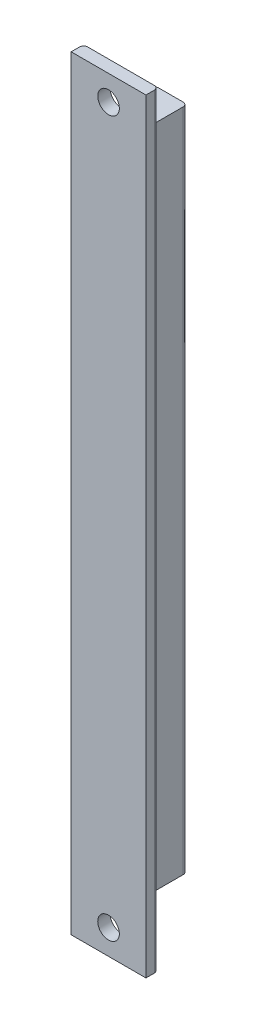
SolidWorks part; units mm, degrees
ref_plane "Front Plane" through (0, 0, 0) normal (0, 0, 1) x (1, 0, 0)
ref_plane "Top Plane" through (0, 0, 0) normal (0, 1, 0) x (1, 0, 0)
ref_plane "Right Plane" through (0, 0, 0) normal (1, 0, 0) x (0, 0, -1)
sketch "Sketch1" plane through (0, 0, 0) normal (0, 1, 0) x (1, 0, 0)
  line L0 (0, 2) -> (-6.1, 2)
  line L5 (11.9, 2) -> (0, 2)
  line L6 (11.9, 2) -> (11.9, 4)
  line L7 (10.9, 5) -> (6.85, 5)
  line L8 (-6.1, 2) -> (-6.1, 4)
  line L9 (-1.05, 5) -> (-5.1, 5)
  line L11 (-1.05, 5) -> (-1.05, 16)
  line L12 (-0.05, 17) -> (5.85, 17)
  line L13 (6.85, 5) -> (6.85, 16)
  arc A0 (11.9, 4) -> (10.9, 5) centre (10.9, 4) ccw
  arc A1 (-6.1, 4) -> (-5.1, 5) centre (-5.1, 4) cw
  arc A2 (6.85, 16) -> (5.85, 17) centre (5.85, 16) ccw
  arc A3 (-0.05, 17) -> (-1.05, 16) centre (-0.05, 16) ccw
  point P17 (11.9, 5)
  point P20 (-6.1, 5)
  point P23 (6.85, 17)
  point P26 (-1.05, 17)
  dimension "D7" = 1
  dimension "D3" = 3
  dimension "D4" = 18
  dimension "D5" = 7.9
  dimension "D6" = 12
extrude "Boss-Extrude1" add sketch "Sketch1" along normal blind 160
sketch "Sketch2" plane through (0, 0, 0) normal (0, -1, 0) x (1, 0, 0)
  line L0 (10.9, -5) -> (6.85, -5) construction
  line L1 (11.9, -2) -> (-6.1, -2)
  line L2 (11.9, -2) -> (11.9, -4)
  line L3 (10.9, -5) -> (-5.1, -5)
  line L4 (-6.1, -2) -> (-6.1, -4)
  arc A0 (-5.1, -5) -> (-6.1, -4) centre (-5.1, -4) cw
  arc A1 (10.9, -5) -> (11.9, -4) centre (10.9, -4) ccw
  dimension "D1" = 1
extrude "Boss-Extrude2" add sketch "Sketch2" along normal blind 12
extrude "Boss-Extrude3" add sketch "Sketch2<2>" against normal blind 12 from surface starting at face at (2.9, 160, -8.2357)
sketch "Sketch2<2>" plane through (0, 0, 0) normal (0, -1, 0) x (1, 0, 0) same geometry as "Sketch2"
sketch "Sketch3" plane through (0, 0, -5) normal (0, 0, -1) x (-1, 0, 0)
  line L0 (-2.9, 172) -> (-2.9, -12) construction
  line L1 (5.1, 172) -> (-10.9, 172) construction
  line L2 (5.1, -12) -> (-10.9, -12) construction
  circle A0 centre (-2.9, 166) radius 2.6
  circle A1 centre (-2.9, -6) radius 2.6
  dimension "D1" = 5.2
  dimension "D2" = 6
  dimension "D3" = 6
extrude "Cut-Extrude1" cut sketch "Sketch3" against normal blind 12
